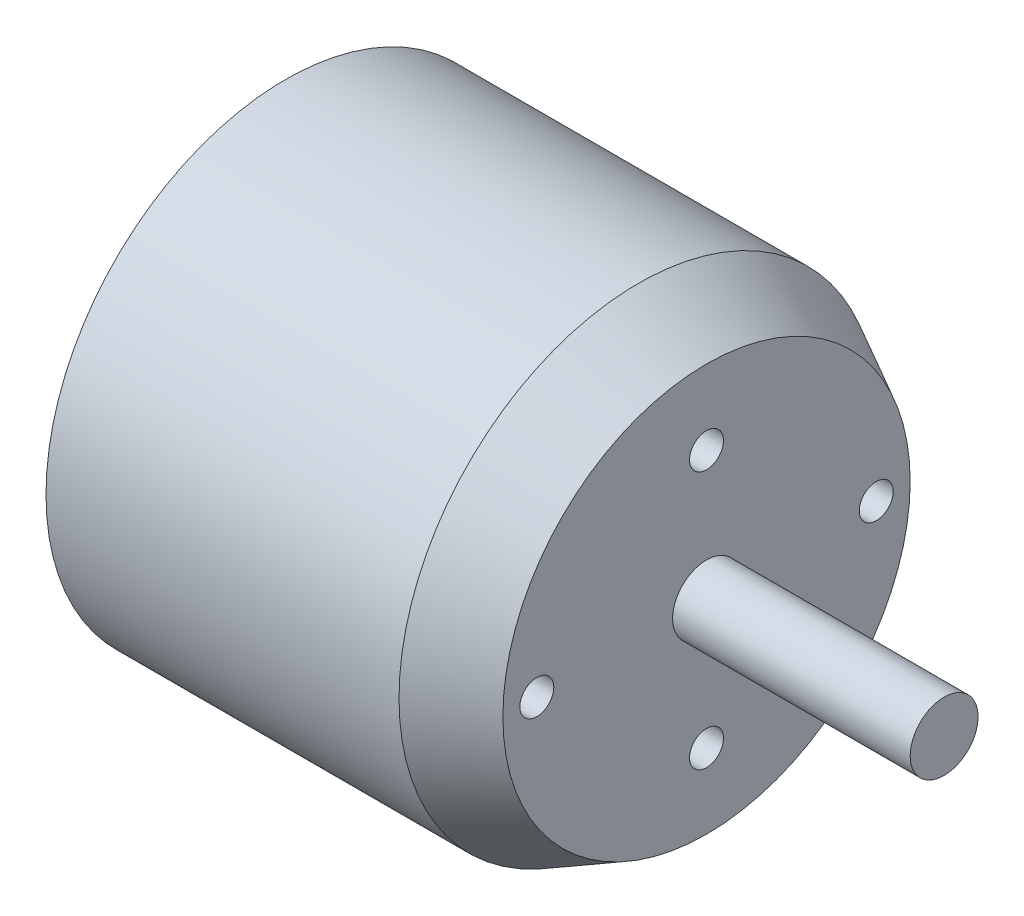
SolidWorks part; units mm, degrees
ref_plane "Front" through (0, 0, 0) normal (0, 0, 1) x (1, 0, 0)
ref_plane "Top" through (0, 0, 0) normal (0, 1, 0) x (1, 0, 0)
ref_plane "Right" through (0, 0, 0) normal (1, 0, 0) x (0, 0, -1)
sketch "Sketch1" plane through (0, 0, 0) normal (0, 0, 1) x (1, 0, 0)
  line L0 (1.2273, 0) -> (20.8636, 0) construction
  line L1 (17.5, 0) -> (17.5, 2.5)
  line L2 (17.5, 2.5) -> (0, 2.5)
  line L3 (0, 2.5) -> (0, 15)
  line L4 (0, 15) -> (-5, 17.65)
  line L5 (-5, 17.65) -> (-31, 17.65)
  line L6 (-31, 17.65) -> (-34, 9)
  line L7 (-36, 2.5) -> (-34, 2.5)
  line L8 (-34, 2.5) -> (-34, 9)
  line L9 (-36, 2.5) -> (-36, 0)
  line L10 (-36, 0) -> (-34, 0)
  line L11 (-34, 0) -> (-34, 2.5)
  line L12 (0, 2.5) -> (0, 0)
  line L13 (0, 0) -> (17.5, 0)
  line L14 (0, 0) -> (-34, 0)
  dimension "D1" = 5
  dimension "D2" = 17.5
  dimension "D3" = 36
  dimension "D4" = 2
  dimension "D5" = 35.3
  dimension "D6" = 30
  dimension "D7" = 5
  dimension "D8" = 18
  dimension "D9" = 3
revolve "Revolve1" add sketch "Sketch1" angle 360 about L0 region at (-16.8174, 8.6016, 0)
revolve "Revolve2" add sketch "Sketch1<3>" angle 360 about L0 region at (8.75, 1.25, 0) region at (-35, 1.25, 0)
sketch "Sketch1<3>" plane through (0, 0, 0) normal (0, 0, 1) x (1, 0, 0) same geometry as "Sketch1"
sketch "Sketch2" plane through (0, 0, 0) normal (1, 0, 0) x (0, 0, -1)
  circle A0 centre (0, 0) radius 12.5 construction
  circle A1 centre (0, 0) radius 9.5 construction
  dimension "D1" = 25
  dimension "D2" = 19
hole_wizard "M3x0.5 Tapped Hole1" positions "Sketch3" profile "Sketch4" tap size "M3x0.5" standard "ANSI Metric"
sketch "Sketch3" plane through (0, 0, 0) normal (1, 0, 0) x (0, 0, -1)
  circle A0 centre (0, 0) radius 9.5 construction
  circle A1 centre (0, 0) radius 12.5 construction
  point P0 (0, 9.5)
  point P4 (0, -9.5)
  point P6 (-12.5, 0)
  point P10 (12.5, 0)
sketch "Sketch4" plane through (0, 9.5, 0) normal (0, 1, 0) x (0, 0, -1)
  line L0 (0, 0) -> (0, 8.2511)
  line L1 (0, 8.2511) -> (1.25, 7.5)
  line L2 (1.25, 7.5) -> (1.25, 0)
  line L5 (1.25, 0) -> (0, 0)
  line L10 (0, 8.2511) -> (-1.25, 7.5) construction
  line L11 (0, -6.35) -> (0, 107.95) construction
  dimension "Tap Drill Dia." = 2.5
  dimension "Tap Drill Depth" = 7.5
  dimension "Drill Angle" = 118
cosmetic thread "Hole Thread1" parameters "D1"=6, "D2"=3
cosmetic thread "Hole Thread2" parameters "D1"=6, "D2"=3
cosmetic thread "Hole Thread3" parameters "D1"=6, "D2"=3
cosmetic thread "Hole Thread4" parameters "D1"=6, "D2"=3
